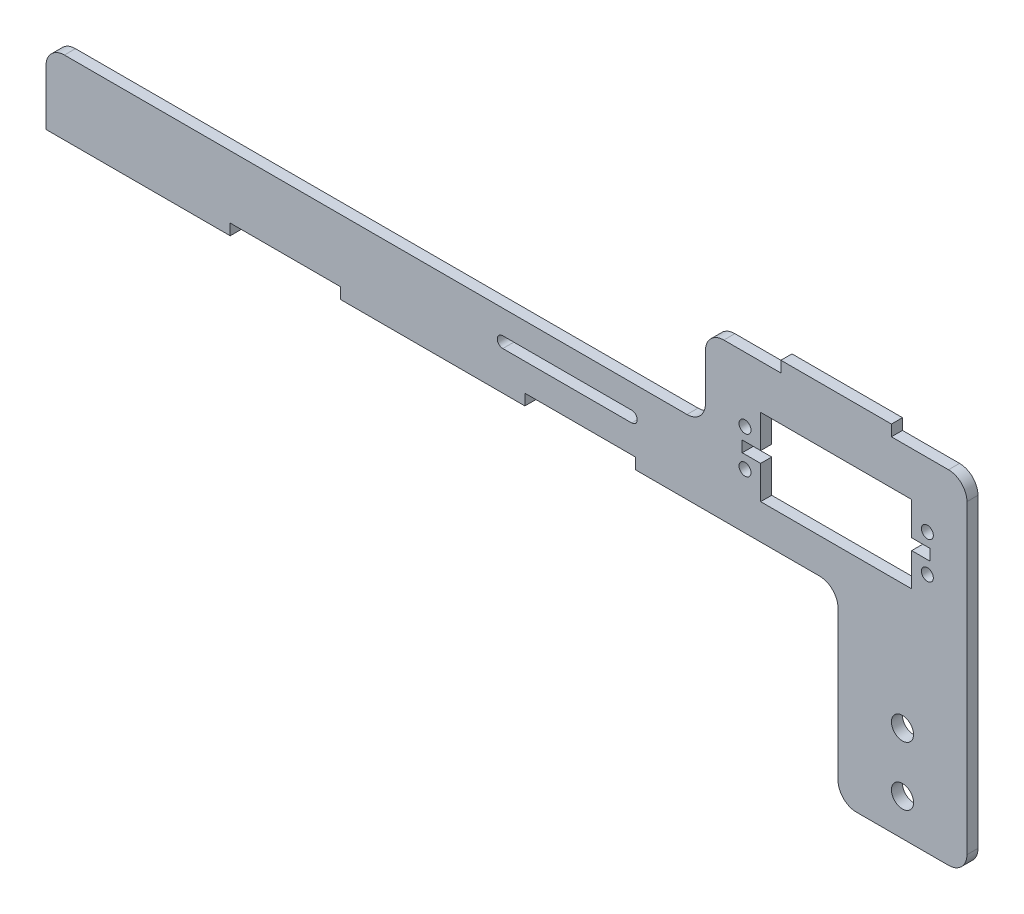
SolidWorks part; units mm, degrees
ref_plane "Plano frontal" through (0, 0, 0) normal (0, 0, 1) x (1, 0, 0)
ref_plane "Plano superior" through (0, 0, 0) normal (0, 1, 0) x (1, 0, 0)
ref_plane "Plano direito" through (0, 0, 0) normal (1, 0, 0) x (0, 0, -1)
sketch "Esboço1" plane through (0, 0, 0) normal (0, 0, 1) x (1, 0, 0)
  line L0 (194, 0) -> (235, 0) construction
  line L1 (215, -20) -> (160, -20)
  line L2 (250, -20) -> (250, 22.5)
  line L4 (0, -20) -> (0, 0)
  line L5 (194, 10.5) -> (235, 10.5)
  line L6 (194, 10.5) -> (194, -10.5)
  line L7 (194, -10.5) -> (235, -10.5)
  line L8 (235, 10.5) -> (235, -10.5)
  line L9 (214.5, 10.5) -> (214.5, -10.5) construction
  line L10 (0, 0) -> (179, 0)
  line L11 (179, 0) -> (179, 22.5)
  line L12 (250, 0) -> (184.4373, 0) construction
  line L13 (50, -20) -> (50, -17)
  line L14 (50, -17) -> (80, -17)
  line L15 (80, -17) -> (80, -20)
  line L16 (130, -20) -> (130, -17)
  line L17 (130, -17) -> (160, -17)
  line L18 (160, -17) -> (160, -20)
  line L19 (50, -20) -> (0, -20)
  line L20 (130, -20) -> (80, -20)
  line L21 (124, -8) -> (159, -8) construction
  line L22 (124, -6.5) -> (159, -6.5)
  line L23 (124, -9.5) -> (159, -9.5)
  line L26 (215, -20) -> (215, -70.5)
  line L27 (215, -70.5) -> (250, -70.5)
  line L28 (250, -20) -> (250, -70.5)
  line L29 (194, 1.5) -> (189, 1.5)
  line L30 (189, 1.5) -> (189, -1.5)
  line L31 (189, -1.5) -> (194, -1.5)
  line L32 (235, 1.5) -> (240, 1.5)
  line L33 (240, 1.5) -> (240, -1.5)
  line L34 (240, -1.5) -> (235, -1.5)
  line L36 (229.5, 25.5) -> (199.5, 25.5)
  line L37 (229.5, 25.5) -> (229.5, 22.5)
  line L38 (229.5, 22.5) -> (199.5, 22.5)
  line L39 (199.5, 25.5) -> (199.5, 22.5)
  line L40 (229.5, 25.5) -> (199.5, 22.5) construction
  line L41 (229.5, 22.5) -> (199.5, 25.5) construction
  line L42 (179, 22.5) -> (250, 22.5)
  circle A0 centre (189.75, 5) radius 1.625
  circle A1 centre (239.25, 5) radius 1.625
  circle A2 centre (239.25, -5) radius 1.625
  circle A3 centre (189.75, -5) radius 1.625
  arc A5 (124, -6.5) -> (124, -9.5) centre (124, -8) ccw
  arc A6 (159, -9.5) -> (159, -6.5) centre (159, -8) ccw
  circle A7 centre (232.5, -60.5) radius 3
  circle A8 centre (232.5, -44.5) radius 3
  point P36 (141.5, -8)
  point P51 (189, 0)
  point P57 (214.5, 24)
  point P62 (214.5, 20)
  dimension "D8" = 3.25
  dimension "D9" = 10
  dimension "D19" = 1.5
  dimension "D27" = 6
  dimension "D29" = 10
  dimension "D30" = 6
  dimension "D3" = 41
  dimension "D4" = 15
  dimension "D5" = 21
  dimension "D6" = 35
  dimension "D7" = 49.5
  dimension "D10" = 20
  dimension "D11" = 15
  dimension "D12" = 179
  dimension "D13" = 50
  dimension "D14" = 30
  dimension "D15" = 3
  dimension "D16" = 50
  dimension "D17" = 30
  dimension "D18" = 3
  dimension "D20" = 8
  dimension "D21" = 35
  dimension "D22" = 20
  dimension "D23" = 12
  dimension "D25" = 9.5
  dimension "D28" = 50.5
  dimension "D31" = 16
  dimension "D32" = 3
  dimension "D33" = 5
  dimension "D34" = 3
  dimension "D35" = 30
extrude "Ressalto-extrusão1" add sketch "Esboço1" along normal blind 3 contours L20 L16 L17 L18 L1 L2 L11 L10 L4 L19 L13 L14 L15 A1 A0 L5 L8 L7 L6 A2 A3 | L36 L39 L37 region at (159.6775, -14.7785, 0) region at (214.5, 24, 0)
fillet "Filete1" radius 5 7 edges at (215, -20, 1.5) (215, -70.5, 1.5) (250, -70.5, 1.5) (179, 0, 1.5) (0, 0, 1.5) (179, 22.5, 1.5) (250, 22.5, 1.5)
